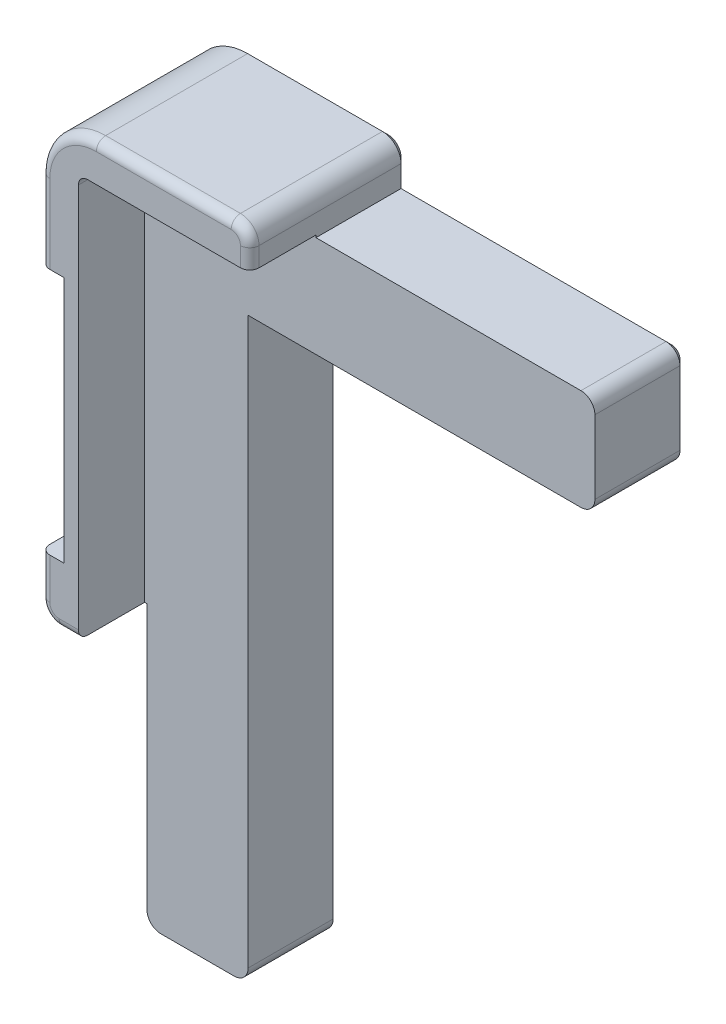
SolidWorks part; units mm, degrees
ref_plane "Front Plane" through (0, 0, 0) normal (0, 0, 1) x (1, 0, 0)
ref_plane "Top Plane" through (0, 0, 0) normal (0, 1, 0) x (1, 0, 0)
ref_plane "Right Plane" through (0, 0, 0) normal (1, 0, 0) x (0, 0, -1)
ref_plane "PZ 20.375" through (0, 0, 20.375) normal (0, 0, 1) x (1, 0, 0)
sketch "body and tongues sketch" plane through (0, 0, 20.375) normal (0, 0, 1) x (1, 0, 0)
  line L0 (-4.42, 7.07) -> (18.08, 7.07)
  line L1 (18.08, 7.07) -> (18.08, 2.75)
  line L2 (18.08, 2.75) -> (48.08, 2.75)
  line L3 (48.08, 2.75) -> (48.08, -8.13)
  line L4 (48.08, -8.13) -> (10.78, -8.13)
  line L5 (10.78, -8.13) -> (10.78, -70.43)
  line L6 (10.78, -70.43) -> (-0.1, -70.43)
  line L7 (-0.1, -70.43) -> (-0.1, -40.43)
  line L8 (-0.1, -40.43) -> (-4.42, -40.43)
  line L9 (-4.42, -40.43) -> (-4.42, 7.07)
extrude "body and tongues" add sketch "body and tongues sketch" along normal mid plane 9.75
ref_plane "PZ 23.935" through (0, 0, 23.935) normal (0, 0, 1) x (1, 0, 0)
sketch "rim sketch" plane through (0, 0, 23.935) normal (0, 0, 1) x (1, 0, 0)
  line L0 (-4.42, 7.07) -> (18.08, 7.07)
  line L1 (18.08, 7.07) -> (18.08, 3)
  line L2 (18.08, 3) -> (-0.35, 3)
  line L3 (-0.35, 3) -> (-0.35, -40.43)
  line L4 (-0.35, -40.43) -> (-4.42, -40.43)
  line L5 (-4.42, -40.43) -> (-4.42, 7.07)
extrude "rim" add sketch "rim sketch" along normal mid plane 16.87
sketch "bracket seat sketch" plane through (0, 0, 23.935) normal (0, 0, 1) x (1, 0, 0)
  line L0 (-1.92, -34) -> (-5.42, -34)
  line L1 (-5.42, -34) -> (-5.42, -7.4)
  line L2 (-5.42, -7.4) -> (-1.92, -7.4)
  line L3 (-1.92, -7.4) -> (-1.92, -34)
extrude "bracket seat" cut sketch "bracket seat sketch" against normal mid plane 18.87
ref_plane "PX 1.580" through (1.58, 0, 0) normal (1, 0, 0) x (0, 0, -1)
sketch "screw pilots sketch" plane through (1.58, 0, 0) normal (1, 0, 0) x (0, 0, -1)
  circle A0 centre (-20.375, -28.7) radius 2.15
  circle A1 centre (-20.375, -12.7) radius 2.15
extrude "screw pilots" cut sketch "screw pilots sketch" against normal mid plane 9
fillet "bumper corner" radius 6 1 edges at (-4.42, 7.07, 23.935) tangent propagation no
fillet "inside corner of the rim" radius 1 1 edges at (-0.35, 3, 28.81) tangent propagation no
fillet "rim ends" radius 2 2 edges at (18.08, 7.07, 23.935) (-4.42, -40.43, 23.935) tangent propagation no
fillet "tongue lead-in" radius 1.5 4 edges at (48.08, -8.13, 20.375) (48.08, 2.75, 20.375) (10.78, -70.43, 20.375) (-0.1, -70.43, 20.375) tangent propagation no
fillet "rim top edge" radius 1 8 edges at (18.08, 4.035, 32.37) (17.4942, 6.4842, 32.37) (-4.42, -3.165, 32.37) (-2.6626, 5.3126, 32.37) (-1.385, -40.43, 32.37) (-3.8342, -39.8442, 32.37) (8.83, 7.07, 32.37) (-4.42, -36.215, 32.37)
chamfer "bed face chamfer" distance 0.6 angle 45 21 edges at (47.6407, 2.3107, 15.5) (32.33, 2.75, 15.5) (18.08, 3.91, 15.5) (17.4942, 6.4842, 15.5) (8.83, 7.07, 15.5) (-2.6626, 5.3126, 15.5) (-4.42, -3.165, 15.5) (-3.17, -7.4, 15.5) (-1.92, -20.7, 15.5) (-3.17, -34, 15.5) (-4.42, -36.215, 15.5) (-3.8342, -39.8442, 15.5) (-1.26, -40.43, 15.5) (-0.1, -54.68, 15.5) (0.3393, -69.9907, 15.5) (5.34, -70.43, 15.5) (10.3407, -69.9907, 15.5) (10.78, -38.53, 15.5) (28.68, -8.13, 15.5) (47.6407, -7.6907, 15.5) (48.08, -2.69, 15.5)
equation "\"diffL\" = 608.8mm"
equation "\"diffW\" = 329.4mm"
equation "\"diffT\" = 2.9mm"
equation "\"chanSlotW\" = 12.9mm"
equation "\"chanSlotDepth\" = 11.13mm"
equation "\"chanFloor\" = 1.57mm"
equation "\"chanLeg\" = 12.7mm"
equation "\"lightL\" = 605mm"
equation "\"lightW\" = 331mm"
equation "\"lightH\" = 92mm"
equation "\"lightSideFlat\" = 30mm"
equation "\"lightSlopeLen\" = 33.1mm"
equation "\"lightWingDepth\" = 47.9mm"
equation "\"lightWingFlat\" = 90.2mm"
equation "\"lightChanW\" = 99.6mm"
equation "\"lightChanStand\" = 44.1mm"
equation "\"insFlangeD\" = 12.3mm"
equation "\"insFromEnd\" = 20.7mm"
equation "\"insUpSlope\" = 20.8mm"
equation "\"gaugeH\" = 10mm"
equation "\"gaugeStepLen\" = 14mm"
equation "\"gaugeStepW0\" = 13.1mm"
equation "\"gaugeStepDW\" = 0.2mm"
equation "\"gaugeSteps\" = 5mm"
equation "\"gaugeHandleLen\" = 30mm"
equation "\"gaugeHandleW\" = 24mm"
equation "\"gaugeSlot0\" = 3mm"
equation "\"gaugeSlotD\" = 0.1mm"
equation "\"gaugeSlotDepth\" = 8mm"
equation "\"gap\" = 25.4mm"
equation "\"edgeL\" = 1mm"
equation "\"edgeW\" = 0.75mm"
equation "\"proud\" = 1.5mm"
equation "\"seatClr\" = 0.15mm"
equation "\"tongueClrZ\" = 0.1mm"
equation "\"tongueClrX\" = 0.25mm"
equation "\"tongueLen\" = 30mm"
equation "\"armSide\" = 45mm"
equation "\"armEnd\" = 20mm"
equation "\"cornerCham\" = 3mm"
equation "\"brkW\" = 26mm"
equation "\"brkT\" = 7mm"
equation "\"brkSeatClr\" = 0.2mm"
equation "\"brkScrewSpan\" = 16mm"
equation "\"pilotD\" = 2.7mm"
equation "\"pilotDepth\" = 10mm"
equation "\"screwClrD\" = 3.9mm"
equation "\"jogBelow\" = 4mm"
equation "\"padT\" = 7mm"
equation "\"padLen\" = 31mm"
equation "\"m6Clr\" = 7mm"
equation "\"m6Slot\" = 3mm"
equation "\"flangeRelD\" = 17mm"
equation "\"flangeRelDepth\" = 1.5mm"
equation "\"relLen\" = 7mm"
equation "\"relDepth\" = 4mm"
equation "\"relLand\" = 2mm"
equation "\"knockN\" = 100mm"
equation "\"petgcfE\" = 3000mm"
equation "\"mockExtent\" = 110mm"
equation "\"relZnear\" = 9.4mm"
equation "\"relZfar\" = 23.4mm"
equation "\"headD\" = 8mm"
equation "\"headH\" = 2.5mm"
equation "\"headFromEnd\" = 6.8mm"
equation "\"headBack\" = 16.4mm"
equation "\"sideClr\" = 0.4mm"
equation "\"cornerRelR\" = 1.5mm"
equation "\"cornerRelBack\" = 0.6mm"
equation "\"endHeadH\" = 2.8mm"
equation "\"footClr\" = 1.2mm"
equation "\"footEndClr\" = 3.5mm"
equation "\"footLift\" = 6mm"
equation "\"footBlockClr\" = 0.5mm"
equation "\"footBack\" = 50mm"
equation "\"footFwd\" = 10mm"
equation "\"footBraceEnd\" = 3mm"
equation "\"footLoadN\" = 25mm"
equation "\"spacerLen\" = 60mm"
equation "\"spacerShort\" = 0.5mm"
equation "\"spacerCham\" = 0.8mm"
equation "\"spacerPerSide\" = 3mm"
equation "\"spacerPerEnd\" = 1mm"
equation "\"toolR\" = 9mm"
equation "\"visR\" = 4mm"
equation "\"edgeR\" = 1mm"
equation "\"bendOutR\" = 5mm"
equation "\"insideR\" = 2.5mm"
equation "\"footCornerR\" = 10mm"
equation "\"footFrontR\" = 8mm"
equation "\"braceKinkR\" = 12mm"
equation "\"bedCham\" = 1mm"
equation "\"bedChamSmall\" = 0.6mm"
equation "\"soleTopR\" = 2mm"
equation "\"cornerR\" = 6mm"
equation "\"rimInR\" = 1mm"
equation "\"insFlangeH\" = 1mm"
equation "\"insHoleFinishD\" = 4.5mm"
equation "\"insLen\" = 6.4mm"
